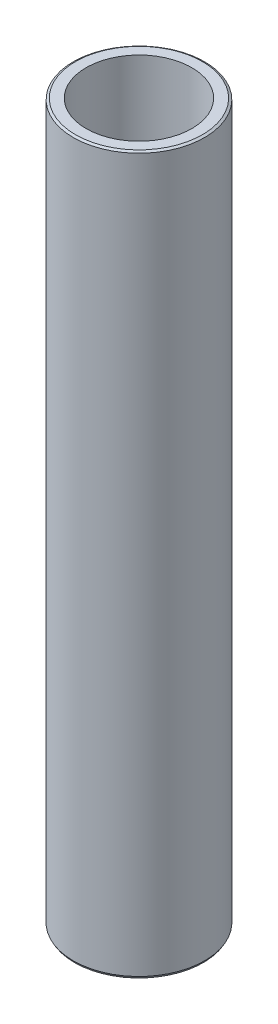
SolidWorks part; units mm, degrees
ref_plane "Front Plane" through (0, 0, 0) normal (0, 0, 1) x (1, 0, 0)
ref_plane "Top Plane" through (0, 0, 0) normal (0, 1, 0) x (1, 0, 0)
ref_plane "Right Plane" through (0, 0, 0) normal (1, 0, 0) x (0, 0, -1)
sketch "Sketch1" plane through (0, 0, 0) normal (0, 1, 0) x (1, 0, 0)
  circle A0 centre (0, 0) radius 55
  dimension "SHAFT_OD" = 110
extrude "Boss-Extrude1" add sketch "Sketch1" along normal blind 600
sketch "Sketch2" plane through (0, 0, 0) normal (0, 1, 0) x (1, 0, 0)
  circle A0 centre (0, 0) radius 44.2521
  dimension "BORE_D" = 88.5042
extrude "Cut-Extrude1" cut sketch "Sketch2" along normal through all
chamfer "Chamfer1" distance 1.0873 angle 60 2 edges at (0, 600, 55) (0, 0, 55) first distance on face at (0, 600, 55) first distance on face at (0, 0, 44.2521)
